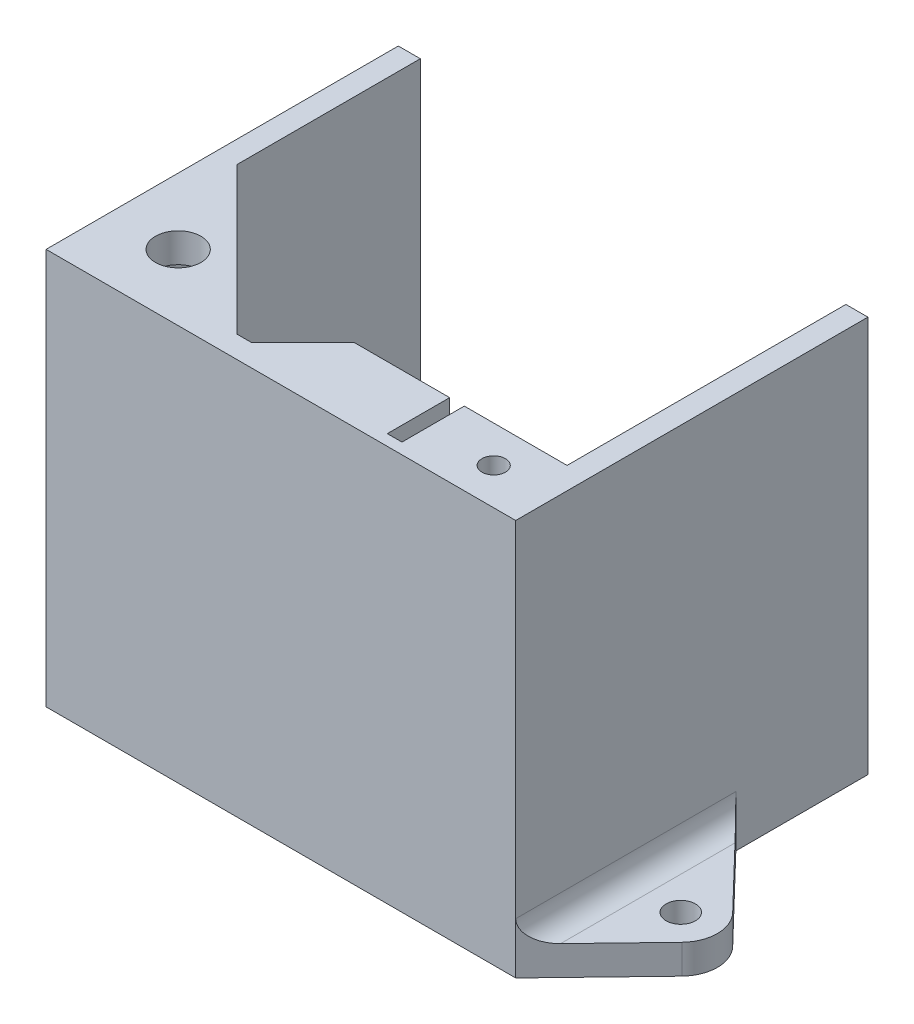
SolidWorks part; units mm, degrees
ref_plane "Płaszczyzna przednia" through (0, 0, 0) normal (0, 0, 1) x (1, 0, 0)
ref_plane "Płaszczyzna górna" through (0, 0, 0) normal (0, 1, 0) x (1, 0, 0)
ref_plane "Płaszczyzna prawa" through (0, 0, 0) normal (1, 0, 0) x (0, 0, -1)
sketch "Sketch1" plane through (0, 0, 0) normal (0, 1, 0) x (1, 0, 0)
  line L1 (-32, 24) -> (32, 24)
  line L2 (-32, 24) -> (-32, -24)
  line L3 (-32, -24) -> (32, -24)
  line L4 (32, 24) -> (32, -24)
  line L5 (-32, 24) -> (32, -24) construction
  line L6 (-32, -24) -> (32, 24) construction
  point P0 (0, 0)
  dimension "D1" = 64
  dimension "D2" = 48
extrude "Boss-Extrude1" add sketch "Sketch1" along normal blind 4
sketch "Sketch2" plane through (0, 0, 0) normal (0, -1, 0) x (1, 0, 0)
  line L9 (-20.8246, -16) -> (-22.4123, -13.25)
  line L10 (-22.4123, -13.25) -> (-25.5877, -13.25)
  line L11 (-25.5877, -13.25) -> (-27.1754, -16)
  line L12 (-27.1754, -16) -> (-25.5877, -18.75)
  line L13 (-25.5877, -18.75) -> (-22.4123, -18.75)
  line L14 (-22.4123, -18.75) -> (-20.8246, -16)
  line L15 (-32, -24) -> (-32, 24) construction
  line L16 (32, -24) -> (-32, -24) construction
  circle A0 centre (-24, -16) radius 2.75 construction
  dimension "D1" = 8
  dimension "D2" = 8
extrude "Cut-Extrude1" cut sketch "Sketch2" against normal blind 2.4
sketch "Sketch4" plane through (0, 0, 0) normal (0, -1, 0) x (1, 0, 0)
  line L0 (-32, -24) -> (-32, 24) construction
  line L1 (9.1754, 10) -> (7.5877, 12.75)
  line L2 (7.5877, 12.75) -> (4.4123, 12.75)
  line L3 (4.4123, 12.75) -> (2.8246, 10)
  line L4 (2.8246, 10) -> (4.4123, 7.25)
  line L5 (4.4123, 7.25) -> (7.5877, 7.25)
  line L6 (7.5877, 7.25) -> (9.1754, 10)
  line L8 (32, -24) -> (-32, -24) construction
  circle A0 centre (6, 10) radius 2.75 construction
  dimension "D1" = 38
  dimension "D2" = 34
extrude "Cut-Extrude2" cut sketch "Sketch4" against normal blind 2.4
sketch "Sketch6" plane through (0, 4, 0) normal (0, 1, 0) x (1, 0, 0)
  line L0 (-29, 21) -> (-29, 24)
  line L1 (-32, 24) -> (32, 24)
  line L2 (-32, 24) -> (-32, -24)
  line L3 (-32, -24) -> (32, -24)
  line L4 (32, 24) -> (32, -24)
  line L5 (-29, 21) -> (29, 21)
  line L6 (-29, 21) -> (-29, -21)
  line L7 (-29, -21) -> (29, -21)
  line L8 (29, 21) -> (29, -21)
  line L9 (-29, 21) -> (29, -21) construction
  line L10 (-29, -21) -> (29, 21) construction
  line L11 (29, 21) -> (29, 24)
  point P6 (0, 0)
  line M1 (32, -24) -> (32, 24)
  line M2 (32, 24) -> (-32, 24)
  line M3 (-32, 24) -> (-32, -24)
  line M4 (-32, -24) -> (32, -24)
  dimension "D1" = 58
  dimension "D2" = 42
extrude "Boss-Extrude3" add sketch "Sketch6" along normal blind 50 contours L11 L8 L7 L6 L0 M2 M3 M4 M1 region at (-29.8, 4, 0)
sketch "Sketch9" plane through (0, 4, 0) normal (0, 1, 0) x (1, 0, 0)
  line L0 (1, -13) -> (-7, -21)
  line L3 (29, -13) -> (1, -13)
  line L5 (-29, -21) -> (29, -21) construction
  line L6 (-7, -21) -> (29, -21)
  line L7 (1, -13) -> (-7, -21)
  line L9 (29, -21) -> (29, -13)
  line M3 (29, -21) -> (29, 24)
  line M6 (-29, -21) -> (29, -21)
  dimension "D1" = 8
  dimension "D2" = 8
  dimension "D3" = 28
extrude "Boss-Extrude4" add sketch "Sketch9" along normal blind 50 contours L3 L0 M3 M6 region at (12.9167, 4, 17.1667)
sketch "Sketch10" plane through (0, 0, 13) normal (0, 0, -1) x (-1, 0, 0)
  line L0 (-29, 54) -> (-29, 4) construction
  line L1 (-27, 39) -> (-1, 39)
  line L2 (-27, 39) -> (-27, 13)
  line L3 (-27, 13) -> (-1, 13)
  line L4 (-1, 39) -> (-1, 13)
  line L5 (-27, 39) -> (-1, 13) construction
  line L6 (-27, 13) -> (-1, 39) construction
  line L7 (-14, 39) -> (-14, 54) construction
  line L9 (-29, 54) -> (-1, 54) construction
  line L15 (-14.9986, 39) -> (-13.0014, 39)
  line L16 (-14.9986, 39) -> (-14.9986, 54)
  line L17 (-14.9986, 54) -> (-13.0014, 54)
  line L18 (-13.0014, 39) -> (-13.0014, 54)
  line L19 (-14.9986, 39) -> (-13.0014, 54) construction
  line L20 (-14.9986, 54) -> (-13.0014, 39) construction
  point P0 (-14, 26)
  point P9 (-14, 46.5)
  line M4 (-1, 4) -> (-1, 54)
  line M5 (-1, 54) -> (-29, 54)
  dimension "D1" = 26
  dimension "D2" = 26
  dimension "D3" = 15
  dimension "D5" = 28
extrude "Cut-Extrude4" cut sketch "Sketch10" against normal blind 9.5 contours L2 L3 L1 M4 | L1 M5 region at (14, 26, 13) region at (14, 46.5, 13)
sketch "Sketch13" plane through (0, 54, 0) normal (0, 1, 0) x (1, 0, 0)
  line L1 (29, -13) -> (-7.9463, -13)
  line L2 (29, -13) -> (29, -14)
  line L3 (29, -14) -> (-7.9463, -14)
  line L4 (-7.9463, -13) -> (-7.9463, -14)
  dimension "D1" = 1
extrude "Cut-Extrude6" cut sketch "Sketch13" against normal blind 32
sketch "Sketch15" plane through (0, 54, 0) normal (0, 1, 0) x (1, 0, 0)
  line L0 (-29, -1) -> (-9, -21)
  line L5 (-29, 24) -> (-29, -21) construction
  line L6 (-29, -21) -> (-7, -21) construction
  line L7 (-29, 24) -> (-29, -21) construction
  line L8 (-29, -1) -> (-29, -21)
  line L9 (-29, -21) -> (-9, -21)
  line L10 (-32, 24) -> (-32, -24) construction
  line L11 (-32, -24) -> (32, -24) construction
  circle A0 centre (-23, -15) radius 3.1
  dimension "D3" = 9
  dimension "D1" = 20
  dimension "D2" = 20
  dimension "D4" = 9
extrude "Boss-Extrude5" add sketch "Sketch15" against normal blind 4
sketch "Sketch17" plane through (0, 54, 0) normal (0, 1, 0) x (1, 0, 0)
  line L0 (32, -24) -> (32, 24) construction
  line L7 (-32, -24) -> (32, -24) construction
  line L8 (24, -19) -> (24, -24) construction
  line L9 (24, -19) -> (32, -19) construction
  line L11 (24, -15.8246) -> (21.25, -17.4123)
  line L12 (21.25, -17.4123) -> (21.25, -20.5877)
  line L13 (21.25, -20.5877) -> (24, -22.1754)
  line L14 (24, -22.1754) -> (26.75, -20.5877)
  line L15 (26.75, -20.5877) -> (26.75, -17.4123)
  line L16 (26.75, -17.4123) -> (24, -15.8246)
  circle A0 centre (24, -19) radius 2.75 construction
  dimension "D1" = 8
  dimension "D2" = 5
extrude "Cut-Extrude7" cut sketch "Sketch17" against normal blind 7
sketch "Sketch18" plane through (0, 0, 14) normal (0, 0, -1) x (-1, 0, 0)
  line L0 (-14.9986, 54) -> (-29, 54) construction
  line L1 (-26.8, 49.5) -> (-21.2, 49.5)
  line L2 (-26.8, 49.5) -> (-26.8, 47)
  line L3 (-26.8, 47) -> (-21.2, 47)
  line L4 (-21.2, 49.5) -> (-21.2, 47)
  line L5 (-32, 54) -> (-32, 0) construction
  point P6 (-24, 49.5)
  dimension "D1" = 7
  dimension "D2" = 2.5
  dimension "D3" = 5.6
  dimension "D4" = 8
extrude "Cut-Extrude8" cut sketch "Sketch18" against normal blind 5
sketch "Sketch19" plane through (0, 54, 0) normal (0, 1, 0) x (1, 0, 0)
  line L0 (24, -22.1754) -> (24, -15.8246) construction
  line L5 (26.75, -17.4123) -> (24, -15.8246) construction
  line L6 (24, -15.8246) -> (26.75, -19) construction
  line L7 (26.75, -20.5877) -> (26.75, -17.4123) construction
  line L8 (26.75, -19) -> (21.25, -19) construction
  line L10 (20.7023, -15.4012) -> (27.2977, -15.4012)
  line L11 (20.7023, -15.4012) -> (20.7023, -22.5988)
  line L12 (20.7023, -22.5988) -> (27.2977, -22.5988)
  line L13 (27.2977, -15.4012) -> (27.2977, -22.5988)
  line L14 (20.7023, -15.4012) -> (27.2977, -22.5988) construction
  line L15 (20.7023, -22.5988) -> (27.2977, -15.4012) construction
  circle A0 centre (24, -19) radius 1.6
extrude "Boss-Extrude8" add sketch "Sketch19" against normal blind 4.5
fillet "Fillet1" radius 1.5 2 edges at (-29, 50, 11) (-19, 50, 21)
sketch "Sketch20" plane through (0, 0, 0) normal (0, -1, 0) x (1, 0, 0)
  line L0 (32, 24) -> (43.1021, 12.4677)
  line L1 (39.5, 9) -> (32, 9) construction
  line L2 (32, -6) -> (43.1021, 5.5323)
  line L3 (-32, -24) -> (-42.9789, -14.5912)
  line L4 (32, -6) -> (32, 24)
  line L6 (-32, 2) -> (-32, -24)
  line L8 (-39.5, -11) -> (-32, -11) construction
  line L9 (-32, 2) -> (-42.9789, -7.4088)
  line L10 (-20.8246, -16) -> (-22.4123, -13.25) construction
  line L11 (-22.4123, -18.75) -> (-20.8246, -16) construction
  line L12 (-25.5877, -18.75) -> (-22.4123, -18.75) construction
  line L13 (-27.1754, -16) -> (-25.5877, -18.75) construction
  line L14 (-25.5877, -13.25) -> (-27.1754, -16) construction
  line L15 (-22.4123, -13.25) -> (-25.5877, -13.25) construction
  line L16 (9.1754, 10) -> (7.5877, 12.75) construction
  line L17 (7.5877, 7.25) -> (9.1754, 10) construction
  line L18 (4.4123, 7.25) -> (7.5877, 7.25) construction
  line L19 (2.8246, 10) -> (4.4123, 7.25) construction
  line L20 (4.4123, 12.75) -> (2.8246, 10) construction
  line L21 (7.5877, 12.75) -> (4.4123, 12.75) construction
  line L22 (-22.4123, -13.25) -> (-25.5877, -13.25) construction
  line L23 (-20.8246, -16) -> (-22.4123, -13.25) construction
  line L24 (-22.4123, -13.25) -> (-25.5877, -13.25) construction
  line L25 (-20.8246, -16) -> (-22.4123, -13.25) construction
  line L26 (32, -24) -> (32, 24)
  line L27 (32, 24) -> (-32, 24)
  line L28 (-32, 24) -> (-32, -24)
  line L29 (-32, -24) -> (32, -24)
  line L30 (32, -6) -> (32, 24)
  line L32 (-32, 2) -> (-32, -24)
  line L36 (9.1754, 10) -> (7.5877, 12.75)
  line L37 (7.5877, 7.25) -> (9.1754, 10)
  line L38 (4.4123, 7.25) -> (7.5877, 7.25)
  line L39 (2.8246, 10) -> (4.4123, 7.25)
  line L40 (4.4123, 12.75) -> (2.8246, 10)
  line L41 (7.5877, 12.75) -> (4.4123, 12.75)
  line L42 (9.1754, 10) -> (7.5877, 12.75) construction
  line L43 (7.5877, 7.25) -> (9.1754, 10) construction
  line L44 (4.4123, 7.25) -> (7.5877, 7.25) construction
  line L45 (2.8246, 10) -> (4.4123, 7.25) construction
  line L46 (4.4123, 12.75) -> (2.8246, 10) construction
  line L47 (7.5877, 12.75) -> (4.4123, 12.75) construction
  line L48 (-20.8246, -16) -> (-22.4123, -13.25)
  line L49 (-22.4123, -18.75) -> (-20.8246, -16)
  line L50 (-25.5877, -18.75) -> (-22.4123, -18.75)
  line L51 (-27.1754, -16) -> (-25.5877, -18.75)
  line L52 (-25.5877, -13.25) -> (-27.1754, -16)
  line L53 (-22.4123, -13.25) -> (-25.5877, -13.25)
  line L54 (-20.8246, -16) -> (-22.4123, -13.25) construction
  line L55 (-22.4123, -18.75) -> (-20.8246, -16) construction
  line L56 (-25.5877, -18.75) -> (-22.4123, -18.75) construction
  line L57 (-27.1754, -16) -> (-25.5877, -18.75) construction
  line L58 (-25.5877, -13.25) -> (-27.1754, -16) construction
  line L59 (-22.4123, -13.25) -> (-25.5877, -13.25) construction
  circle A0 centre (39.5, 9) radius 2
  circle A1 centre (-39.5, -11) radius 2
  arc A2 (43.1021, 5.5323) -> (43.1021, 12.4677) centre (39.5, 9) ccw
  arc A3 (-42.5162, -7.0122) -> (-42.5162, -14.9878) centre (-39.5, -11) ccw
  dimension "D1" = 0
  dimension "D2" = 0
  dimension "D3" = 0
extrude "Boss-Extrude9" add sketch "Sketch20" against normal blind 4 contours L9 A3 L3 L23 A1 | L2 A2 L0 L4 A0 region at (36.4432, 0, 9) region at (-36.5396, 0, -11)
fillet "Fillet2" radius 3 2 edges at (-32, 4, -11) (32, 4, 9)
